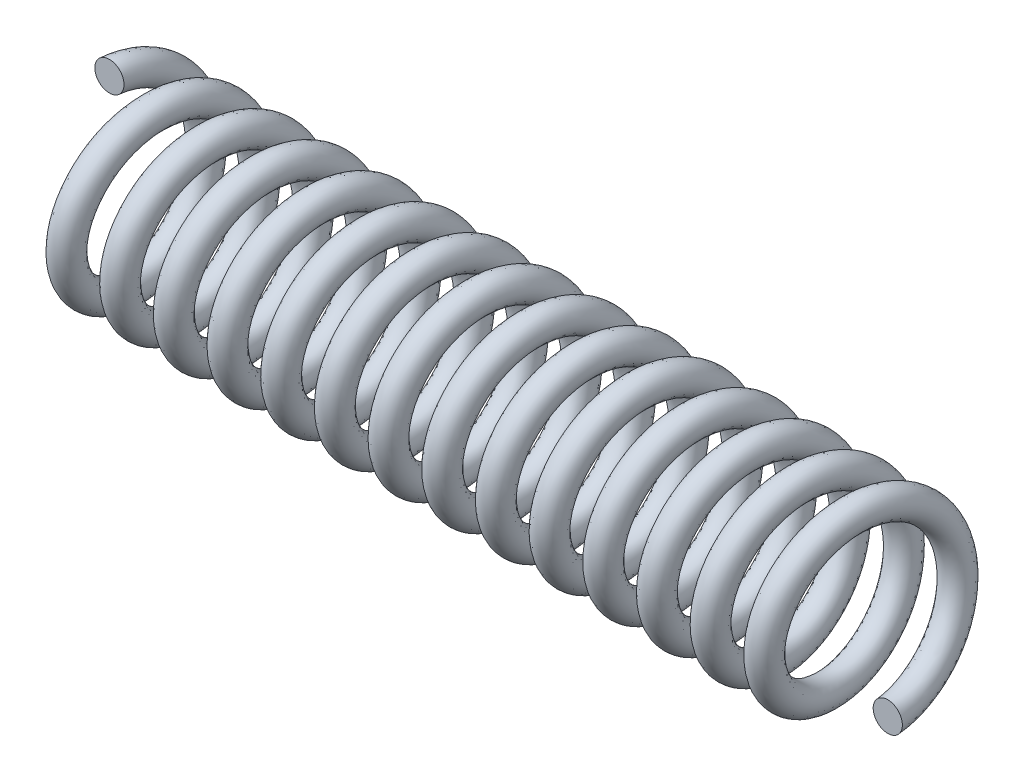
SolidWorks part; units mm, degrees
material "Медь"
ref_plane "Спереди" through (0, 0, 0) normal (0, 0, 1) x (1, 0, 0)
ref_plane "Сверху" through (0, 0, 0) normal (0, 1, 0) x (1, 0, 0)
ref_plane "Справа" through (0, 0, 0) normal (1, 0, 0) x (0, 0, -1)
sketch "Эскиз1" plane through (0, 0, 0) normal (1, 0, 0) x (0, 0, -1)
  circle A2 centre (0, 0) radius 2.125
  dimension "D3" = 4.25
curve "Спираль1" pitch 1.3793 height 20 turns 14.5
sketch "Эскиз3" plane through (0, 0, 0) normal (0, 0, 1) x (1, 0, 0)
  circle A0 centre (0, 2.125) radius 0.375
  spline S0 degree 3 poles (0, 2.125) (0.0286, 2.125) (0.0863, 2.0144) (0.1724, 1.5417) (0.2586, 0.8344) (0.3448, 0) (0.431, -0.8344) (0.5172, -1.5417) (0.6034, -2.0144) (0.6897, -2.1803) (0.7759, -2.0144) (0.8621, -1.5417) (0.9483, -0.8344) (1.0345, 0) (1.1207, 0.8344) (1.2069, 1.5417) (1.2931, 2.0144) (1.3793, 2.1803) (1.4655, 2.0144) (1.5517, 1.5417) (1.6379, 0.8344) (1.7241, 0) (1.8103, -0.8344) (1.8966, -1.5417) (1.9828, -2.0144) (2.069, -2.1803) (2.1552, -2.0144) (2.2414, -1.5417) (2.3276, -0.8344) (2.4138, 0) (2.5, 0.8344) (2.5862, 1.5417) (2.6724, 2.0144) (2.7586, 2.1803) (2.8448, 2.0144) (2.931, 1.5417) (3.0172, 0.8344) (3.1034, 0) (3.1897, -0.8344) (3.2759, -1.5417) (3.3621, -2.0144) (3.4483, -2.1803) (3.5345, -2.0144) (3.6207, -1.5417) (3.7069, -0.8344) (3.7931, 0) (3.8793, 0.8344) (3.9655, 1.5417) (4.0517, 2.0144) (4.1379, 2.1803) (4.2241, 2.0144) (4.3103, 1.5417) (4.3966, 0.8344) (4.4828, 0) (4.569, -0.8344) (4.6552, -1.5417) (4.7414, -2.0144) (4.8276, -2.1803) (4.9138, -2.0144) (5, -1.5417) (5.0862, -0.8344) (5.1724, 0) (5.2586, 0.8344) (5.3448, 1.5417) (5.431, 2.0144) (5.5172, 2.1803) (5.6034, 2.0144) (5.6897, 1.5417) (5.7759, 0.8344) (5.8621, 0) (5.9483, -0.8344) (6.0345, -1.5417) (6.1207, -2.0144) (6.2069, -2.1803) (6.2931, -2.0144) (6.3793, -1.5417) (6.4655, -0.8344) (6.5517, 0) (6.6379, 0.8344) (6.7241, 1.5417) (6.8103, 2.0144) (6.8966, 2.1803) (6.9828, 2.0144) (7.069, 1.5417) (7.1552, 0.8344) (7.2414, 0) (7.3276, -0.8344) (7.4138, -1.5417) (7.5, -2.0144) (7.5862, -2.1803) (7.6724, -2.0144) (7.7586, -1.5417) (7.8448, -0.8344) (7.931, 0) (8.0172, 0.8344) (8.1034, 1.5417) (8.1897, 2.0144) (8.2759, 2.1803) (8.3621, 2.0144) (8.4483, 1.5417) (8.5345, 0.8344) (8.6207, 0) (8.7069, -0.8344) (8.7931, -1.5417) (8.8793, -2.0144) (8.9655, -2.1803) (9.0517, -2.0144) (9.1379, -1.5417) (9.2241, -0.8344) (9.3103, 0) (9.3966, 0.8344) (9.4828, 1.5417) (9.569, 2.0144) (9.6552, 2.1803) (9.7414, 2.0144) (9.8276, 1.5417) (9.9138, 0.8344) (10, 0) (10.0862, -0.8344) (10.1724, -1.5417) (10.2586, -2.0144) (10.3448, -2.1803) (10.431, -2.0144) (10.5172, -1.5417) (10.6034, -0.8344) (10.6897, 0) (10.7759, 0.8344) (10.8621, 1.5417) (10.9483, 2.0144) (11.0345, 2.1803) (11.1207, 2.0144) (11.2069, 1.5417) (11.2931, 0.8344) (11.3793, 0) (11.4655, -0.8344) (11.5517, -1.5417) (11.6379, -2.0144) (11.7241, -2.1803) (11.8103, -2.0144) (11.8966, -1.5417) (11.9828, -0.8344) (12.069, 0) (12.1552, 0.8344) (12.2414, 1.5417) (12.3276, 2.0144) (12.4138, 2.1803) (12.5, 2.0144) (12.5862, 1.5417) (12.6724, 0.8344) (12.7586, 0) (12.8448, -0.8344) (12.931, -1.5417) (13.0172, -2.0144) (13.1034, -2.1803) (13.1897, -2.0144) (13.2759, -1.5417) (13.3621, -0.8344) (13.4483, 0) (13.5345, 0.8344) (13.6207, 1.5417) (13.7069, 2.0144) (13.7931, 2.1803) (13.8793, 2.0144) (13.9655, 1.5417) (14.0517, 0.8344) (14.1379, 0) (14.2241, -0.8344) (14.3103, -1.5417) (14.3966, -2.0144) (14.4828, -2.1803) (14.569, -2.0144) (14.6552, -1.5417) (14.7414, -0.8344) (14.8276, 0) (14.9138, 0.8344) (15, 1.5417) (15.0862, 2.0144) (15.1724, 2.1803) (15.2586, 2.0144) (15.3448, 1.5417) (15.431, 0.8344) (15.5172, 0) (15.6034, -0.8344) (15.6897, -1.5417) (15.7759, -2.0144) (15.8621, -2.1803) (15.9483, -2.0144) (16.0345, -1.5417) (16.1207, -0.8344) (16.2069, 0) (16.2931, 0.8344) (16.3793, 1.5417) (16.4655, 2.0144) (16.5517, 2.1803) (16.6379, 2.0144) (16.7241, 1.5417) (16.8103, 0.8344) (16.8966, 0) (16.9828, -0.8344) (17.069, -1.5417) (17.1552, -2.0144) (17.2414, -2.1803) (17.3276, -2.0144) (17.4138, -1.5417) (17.5, -0.8344) (17.5862, 0) (17.6724, 0.8344) (17.7586, 1.5417) (17.8448, 2.0144) (17.931, 2.1803) (18.0172, 2.0144) (18.1034, 1.5417) (18.1897, 0.8344) (18.2759, 0) (18.3621, -0.8344) (18.4483, -1.5417) (18.5345, -2.0144) (18.6207, -2.1803) (18.7069, -2.0144) (18.7931, -1.5417) (18.8793, -0.8344) (18.9655, 0) (19.0517, 0.8344) (19.1379, 1.5417) (19.2241, 2.0144) (19.3103, 2.1803) (19.3966, 2.0144) (19.4828, 1.5417) (19.569, 0.8344) (19.6552, 0) (19.7414, -0.8344) (19.8276, -1.5417) (19.9137, -2.0144) (19.9714, -2.125) (20, -2.125) knots 0 0 0 0 0.00431 0.008621 0.012931 0.017241 0.021552 0.025862 0.030172 0.034483 0.038793 0.043103 0.047414 0.051724 0.056034 0.060345 0.064655 0.068966 0.073276 0.077586 0.081897 0.086207 0.090517 0.094828 0.099138 0.103448 0.107759 0.112069 0.116379 0.12069 0.125 0.12931 0.133621 0.137931 0.142241 0.146552 0.150862 0.155172 0.159483 0.163793 0.168103 0.172414 0.176724 0.181034 0.185345 0.189655 0.193966 0.198276 0.202586 0.206897 0.211207 0.215517 0.219828 0.224138 0.228448 0.232759 0.237069 0.241379 0.24569 0.25 0.25431 0.258621 0.262931 0.267241 0.271552 0.275862 0.280172 0.284483 0.288793 0.293103 0.297414 0.301724 0.306034 0.310345 0.314655 0.318966 0.323276 0.327586 0.331897 0.336207 0.340517 0.344828 0.349138 0.353448 0.357759 0.362069 0.366379 0.37069 0.375 0.37931 0.383621 0.387931 0.392241 0.396552 0.400862 0.405172 0.409483 0.413793 0.418103 0.422414 0.426724 0.431034 0.435345 0.439655 0.443966 0.448276 0.452586 0.456897 0.461207 0.465517 0.469828 0.474138 0.478448 0.482759 0.487069 0.491379 0.49569 0.5 0.50431 0.508621 0.512931 0.517241 0.521552 0.525862 0.530172 0.534483 0.538793 0.543103 0.547414 0.551724 0.556034 0.560345 0.564655 0.568966 0.573276 0.577586 0.581897 0.586207 0.590517 0.594828 0.599138 0.603448 0.607759 0.612069 0.616379 0.62069 0.625 0.62931 0.633621 0.637931 0.642241 0.646552 0.650862 0.655172 0.659483 0.663793 0.668103 0.672414 0.676724 0.681034 0.685345 0.689655 0.693966 0.698276 0.702586 0.706897 0.711207 0.715517 0.719828 0.724138 0.728448 0.732759 0.737069 0.741379 0.74569 0.75 0.75431 0.758621 0.762931 0.767241 0.771552 0.775862 0.780172 0.784483 0.788793 0.793103 0.797414 0.801724 0.806034 0.810345 0.814655 0.818966 0.823276 0.827586 0.831897 0.836207 0.840517 0.844828 0.849138 0.853448 0.857759 0.862069 0.866379 0.87069 0.875 0.87931 0.883621 0.887931 0.892241 0.896552 0.900862 0.905172 0.909483 0.913793 0.918103 0.922414 0.926724 0.931034 0.935345 0.939655 0.943966 0.948276 0.952586 0.956897 0.961207 0.965517 0.969828 0.974138 0.978448 0.982759 0.987069 0.991379 0.99569 1 1 1 1 construction
sweep "По траектории1" add profiles "Эскиз3" path "Спираль1"
